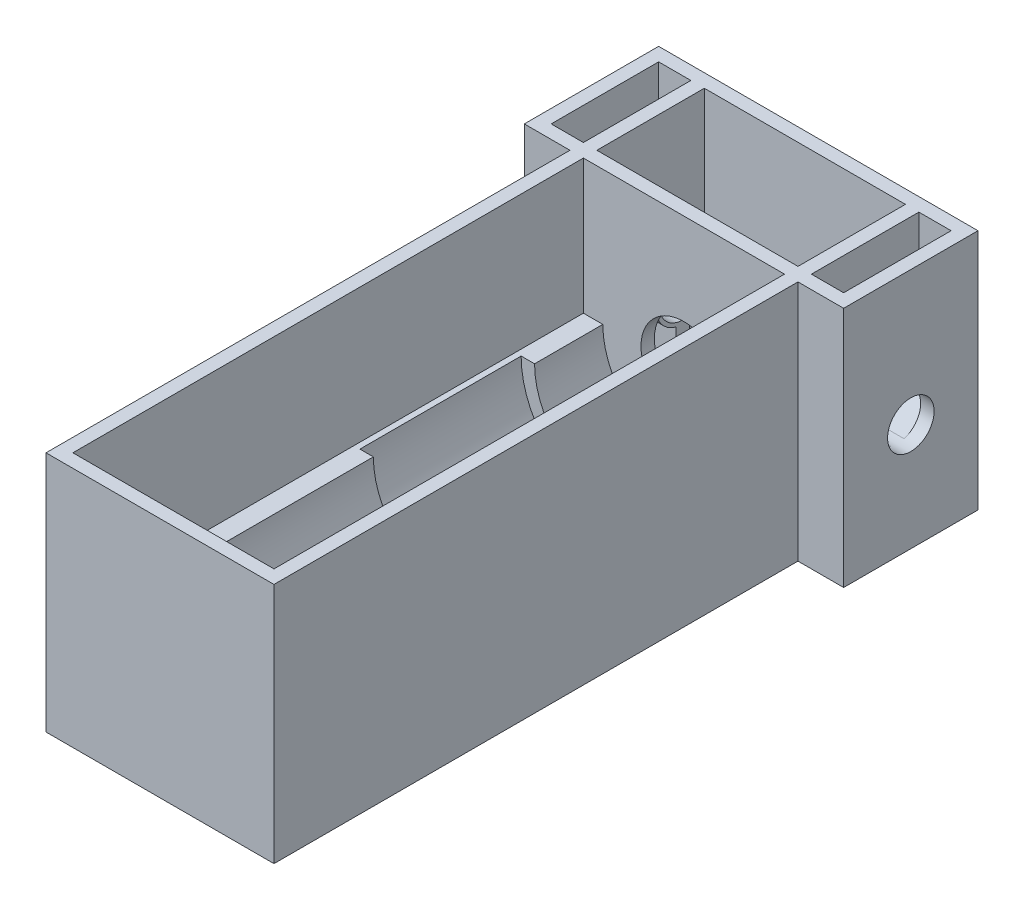
SolidWorks part; units mm, degrees
ref_plane "Front Plane" through (0, 0, 0) normal (0, 0, 1) x (1, 0, 0)
ref_plane "Top Plane" through (0, 0, 0) normal (0, 1, 0) x (1, 0, 0)
ref_plane "Right Plane" through (0, 0, 0) normal (1, 0, 0) x (0, 0, -1)
sketch "Sketch1" plane through (0, 0, 0) normal (0, 0, 1) x (1, 0, 0)
  line L1 (-26.9397, 0) -> (26.9397, 0)
  line L2 (-26.9397, 0) -> (-26.9397, 6.35)
  line L3 (-23.7647, 6.35) -> (23.7647, 6.35)
  line L4 (26.9397, 0) -> (26.9397, 6.35)
  line L6 (-26.9397, 6.35) -> (-26.9397, 57.15)
  line L7 (-26.9397, 57.15) -> (-23.7647, 57.15)
  line L8 (-23.7647, 6.35) -> (-23.7647, 57.15)
  line L10 (26.9397, 6.35) -> (26.9397, 57.15)
  line L11 (26.9397, 57.15) -> (23.7647, 57.15)
  line L12 (23.7647, 6.35) -> (23.7647, 57.15)
  dimension "D1" = 3.175
  dimension "D2" = 53.8795
  dimension "D3" = 6.35
  dimension "D4" = 50.8
extrude "Boss-Extrude1" add sketch "Sketch1" along normal mid plane 25.4
sketch "Sketch2" plane through (0, 0, -12.7) normal (0, 0, -1) x (-1, 0, 0)
  line L0 (26.9397, 0) -> (-26.9397, 0) construction
  line L1 (-26.9397, 57.15) -> (26.9397, 57.15)
  line L2 (-26.9397, 57.15) -> (-26.9397, 0)
  line L3 (-26.9397, 0) -> (26.9397, 0)
  line L4 (26.9397, 57.15) -> (26.9397, 0)
extrude "Boss-Extrude2" add sketch "Sketch2" along normal blind 3.175
sketch "Sketch6" plane through (0, 0, 0) normal (0, 0, 1) x (1, 0, 0)
  line L0 (-23.7647, 25.4) -> (-16.1447, 25.4)
  line L3 (-16.1447, 25.4) -> (-16.1447, 31.75)
  line L4 (-16.1447, 31.75) -> (-21.2247, 31.75)
  line L5 (-21.2247, 31.75) -> (-23.7647, 33.02)
  line L6 (0, 25.4) -> (0, 0) construction
  line L7 (-23.7647, 33.02) -> (-23.7647, 25.4)
  line L9 (-23.7647, 6.35) -> (-23.7647, 57.15) construction
  line L10 (23.7647, 33.02) -> (23.7647, 25.4)
  line L11 (21.2247, 31.75) -> (23.7647, 33.02)
  line L12 (16.1447, 31.75) -> (21.2247, 31.75)
  line L13 (16.1447, 25.4) -> (16.1447, 31.75)
  line L15 (23.7647, 25.4) -> (16.1447, 25.4)
  dimension "D1" = 6.35
  dimension "D2" = 5.08
  dimension "D3" = 7.62
  dimension "D4" = 7.62
  dimension "D5" = 25.4
revolve "Revolve2" add sketch "Sketch6" angle 360 about L0
sketch "Sketch3" plane through (0, 0, 0) normal (1, 0, 0) x (0, 0, -1)
  circle A0 centre (0, 25.4) radius 5.5
  circle A1 centre (0, 25.4) radius 6.35 construction
  dimension "D2" = 11
extrude "Cut-Extrude2" cut sketch "Sketch3" against normal through all both and the other way through all
sketch "Sketch5" plane through (0, 0, 0) normal (0, -1, 0) x (1, 0, 0)
  line L1 (26.9397, -15.875) -> (-26.9397, -15.875)
  line L2 (26.9397, -15.875) -> (26.9397, -41.275)
  line L3 (26.9397, -41.275) -> (-26.9397, -41.275)
  line L4 (-26.9397, -15.875) -> (-26.9397, -41.275)
  circle A0 centre (7.8897, -28.575) radius 3.4925
  circle A1 centre (-17.5103, -28.575) radius 3.4925
  point P9 (26.9397, -28.575)
  dimension "D2" = 6.985
  dimension "D1" = 25.4
  dimension "D3" = 19.05
  dimension "D4" = 2
extrude "Boss-Extrude3" add sketch "Sketch5" against normal blind 6.35
sketch "Sketch7" plane through (0, 0, 0) normal (0, 0, 1) x (1, 0, 0)
  line L0 (23.7647, 6.35) -> (-23.7647, 6.35) construction
  line L1 (-23.7647, 21.9594) -> (-16.1447, 21.9594)
  line L2 (-23.7647, 21.9594) -> (-23.7647, 6.35)
  line L3 (-23.7647, 6.35) -> (-16.1447, 6.35)
  line L4 (-16.1447, 21.9594) -> (-16.1447, 6.35)
  line L5 (-23.7647, 21.9594) -> (-16.1447, 6.35) construction
  line L6 (-23.7647, 6.35) -> (-16.1447, 21.9594) construction
  line L8 (0, 0) -> (0, 25.6446) construction
  line L9 (-26.9397, 0) -> (26.9397, 0) construction
  line L10 (23.7647, 6.35) -> (16.1447, 21.9594) construction
  line L11 (23.7647, 21.9594) -> (16.1447, 6.35) construction
  line L12 (16.1447, 21.9594) -> (16.1447, 6.35)
  line L13 (23.7647, 6.35) -> (16.1447, 6.35)
  line L14 (23.7647, 21.9594) -> (23.7647, 6.35)
  line L15 (23.7647, 21.9594) -> (16.1447, 21.9594)
  line L16 (-23.7647, 6.35) -> (-23.7647, 57.15) construction
  line L17 (-16.1447, 19.05) -> (-16.1447, 31.75) construction
  point P4 (-19.9547, 14.1547)
  point P18 (19.9547, 14.1547)
extrude "Boss-Extrude7" add sketch "Sketch7" along normal mid plane 3.175
sketch "Sketch8" plane through (0, 0, 12.7) normal (0, 0, 1) x (1, 0, 0)
  line L1 (-26.9397, 57.15) -> (26.9397, 57.15)
  line L2 (-26.9397, 57.15) -> (-26.9397, 0)
  line L3 (-26.9397, 0) -> (26.9397, 0)
  line L4 (26.9397, 57.15) -> (26.9397, 0)
  line L5 (-26.9397, 57.15) -> (26.9397, 0) construction
  line L6 (-26.9397, 0) -> (26.9397, 57.15) construction
  point P4 (0, 28.575)
extrude "Boss-Extrude8" add sketch "Sketch8" along normal blind 127
sketch "Sketch9" plane through (0, 0, 0) normal (1, 0, 0) x (0, 0, -1)
  line L0 (0, 25.4) -> (-139.7, 25.4) construction
  line L1 (-139.7, 0) -> (-139.7, 57.15) construction
  line L2 (-70.104, 47.752) -> (-70.104, 44.577)
  line L3 (-70.104, 47.752) -> (-32.004, 47.752)
  line L4 (-32.004, 47.752) -> (-32.004, 44.577)
  line L5 (-32.004, 44.577) -> (-20.1041, 44.577)
  line L6 (0, 35.56) -> (0, 25.4)
  line L7 (0, 25.4) -> (12.7, 25.4) construction
  line L8 (12.7, 6.35) -> (12.7, 57.15) construction
  line L9 (0, 25.4) -> (-70.104, 25.4)
  line L10 (-70.104, 44.577) -> (-136.525, 44.577)
  line L11 (-136.525, 44.577) -> (-136.525, 25.4)
  line L12 (-136.525, 25.4) -> (-70.104, 25.4)
  line L13 (-20.1041, 44.577) -> (-20.1041, 35.56)
  line L14 (-20.1041, 35.56) -> (0, 35.56)
  dimension "D1" = 38.1
  dimension "D2" = 10.16
  dimension "D3" = 22.352
  dimension "D4" = 3.175
  dimension "D5" = 3.175
revolve "Cut-Revolve1" cut sketch "Sketch9" angle 360 about L9
ref_axis "Axis2" through (0, 25.4, 70.104) along (0, 0, -1)
ref_axis "Axis3" through (-26.9397, 25.4, 0) along (1, 0, 0)
ref_plane "Plane2" through (0, 25.4, 0) normal (0, -1, 0) x (-1, 0, 0)
sketch "Sketch13" plane through (0, 0, 0) normal (0, -1, 0) x (-1, 0, 0)
  line L0 (26.9397, -139.7) -> (26.9397, 41.275) construction
  line L1 (26.9397, -15.4709) -> (26.9421, -15.4709)
  line L2 (26.9397, -15.4709) -> (26.9397, -139.7)
  line L3 (26.9397, -139.7) -> (26.9421, -139.7)
  line L4 (26.9421, -15.4709) -> (26.9421, -139.7)
  line L5 (26.9397, -15.4709) -> (26.9421, -139.7) construction
  line L6 (26.9397, -139.7) -> (26.9421, -15.4709) construction
  line L7 (26.9397, -139.7) -> (-26.9397, -139.7) construction
  line L9 (-26.9397, -139.7) -> (-26.9374, -139.7)
  line L10 (-26.9397, -139.7) -> (-26.9397, -15.4709)
  line L11 (-26.9397, -15.4709) -> (-26.9374, -15.4709)
  line L12 (-26.9374, -139.7) -> (-26.9374, -15.4709)
  line L13 (-26.9397, -139.7) -> (-26.9374, -15.4709) construction
  line L14 (-26.9397, -15.4709) -> (-26.9374, -139.7) construction
  point P4 (26.9409, -77.5855)
  point P13 (-26.9386, -77.5855)
extrude "Cut-Extrude7" cut sketch "Sketch13" against normal through all both and the other way through all
sketch "Sketch14" plane through (0, 57.15, 0) normal (0, 1, 0) x (1, 0, 0)
  line L1 (23.7624, -136.525) -> (-23.7647, -136.525)
  line L2 (23.7624, -136.525) -> (23.7624, -15.875)
  line L3 (23.7624, -15.875) -> (-23.7647, -15.875)
  line L4 (-23.7647, -136.525) -> (-23.7647, -15.875)
  line L5 (23.7624, -136.525) -> (-23.7647, -15.875) construction
  line L6 (23.7624, -15.875) -> (-23.7647, -136.525) construction
  line L7 (26.9374, -139.7) -> (-26.9397, -139.7) construction
  line L8 (26.9374, -139.7) -> (26.9374, -15.4709) construction
  line L10 (23.7647, -12.7) -> (-23.7647, -12.7) construction
  line L11 (-26.9397, -139.7) -> (-26.9397, 15.875) construction
  point P4 (-0.0012, -76.2)
  dimension "D1" = 3.175
  dimension "D2" = 3.175
  dimension "D3" = 3.175
  dimension "D4" = 3.175
extrude "Cut-Extrude8" cut sketch "Sketch14" against normal up to surface (31.75 mm away) up to plane "Plane2"
sketch "Sketch15" plane through (0, 0, 20.1041) normal (0, 0, 1) x (1, 0, 0)
  line L2 (-10.16, 25.4) -> (-19.177, 25.4)
  line L3 (19.177, 25.4) -> (10.16, 25.4)
  line L4 (-10.16, 25.4) -> (-19.177, 25.4)
  line L5 (19.177, 25.4) -> (10.16, 25.4)
  arc A2 (-19.177, 25.4) -> (19.177, 25.4) centre (0, 25.4) ccw
  arc A3 (-10.16, 25.4) -> (10.16, 25.4) centre (0, 25.4) ccw
  arc A4 (-19.177, 25.4) -> (19.177, 25.4) centre (0, 25.4) ccw
  arc A5 (-10.16, 25.4) -> (10.16, 25.4) centre (0, 25.4) ccw
  dimension "D1" = 0
extrude "Cut-Extrude9" cut sketch "Sketch15" against normal up to surface (4.2291 mm away) up to face at (-0.0008, 37.6767, 15.875)
sketch "Sketch16" plane through (0, 6.35, 0) normal (0, 1, 0) x (1, 0, 0)
  line L1 (26.9397, 41.275) -> (-26.9397, 41.275)
  line L2 (26.9397, 41.275) -> (26.9397, 15.875)
  line L3 (26.9397, 15.875) -> (-26.9397, 15.875)
  line L4 (-26.9397, 41.275) -> (-26.9397, 15.875)
  line L5 (26.9397, 41.275) -> (-26.9397, 15.875) construction
  line L6 (26.9397, 15.875) -> (-26.9397, 41.275) construction
  point P4 (0, 28.575)
extrude "Cut-Extrude10" cut sketch "Sketch16" against normal through all
sketch "Sketch18" plane through (0, 0, 0) normal (0, 1, 0) x (1, 0, 0)
  line L0 (-26.9397, 15.875) -> (26.9397, 15.875) construction
  line L1 (-23.7647, 15.875) -> (-37.7347, 15.875)
  line L2 (-23.7647, 15.875) -> (-23.7647, -15.875)
  line L3 (-23.7647, -15.875) -> (-37.7347, -15.875)
  line L4 (-37.7347, 15.875) -> (-37.7347, -15.875)
  line L5 (-23.7647, 15.875) -> (-37.7347, -15.875) construction
  line L6 (-23.7647, -15.875) -> (-37.7347, 15.875) construction
  line L7 (-23.7647, -12.7) -> (-23.7647, 12.7) construction
  line L8 (-19.177, -15.875) -> (-23.7647, -15.875) construction
  line L9 (-26.9397, -139.7) -> (-26.9397, 15.875) construction
  line L10 (-34.5597, 12.7) -> (-26.9397, 12.7)
  line L11 (-34.5597, 12.7) -> (-34.5597, -12.7)
  line L12 (-34.5597, -12.7) -> (-26.9397, -12.7)
  line L13 (-26.9397, 12.7) -> (-26.9397, -12.7)
  line L14 (-34.5597, 12.7) -> (-26.9397, -12.7) construction
  line L15 (-34.5597, -12.7) -> (-26.9397, 12.7) construction
  point P4 (-30.7497, 0)
  point P15 (-30.7497, 0)
  dimension "D1" = 7.62
  dimension "D2" = 3.175
  dimension "D3" = 3.175
extrude "Boss-Extrude10" add sketch "Sketch18" along normal up to surface (57.15 mm away) up to face at (-0.0012, 57.15, 76.2)
sketch "Sketch19" plane through (0, 0, 0) normal (1, 0, 0) x (0, 0, -1)
  line L0 (1.5875, 20.1341) -> (12.7, 23.4841)
  line L1 (12.7, 6.35) -> (12.7, 57.15) construction
  line L2 (-1.5875, 20.1341) -> (-12.7, 23.4841)
  line L3 (-12.7, 15.24) -> (-12.7, 35.56) construction
  line L4 (-12.7, 23.4841) -> (-12.7, 0)
  line L5 (-12.7, 0) -> (12.7, 0)
  line L6 (12.7, 0) -> (12.7, 23.4841)
  arc A0 (-1.5875, 20.1341) -> (1.5875, 20.1341) centre (0, 25.4) ccw
  circle A1 centre (0, 25.4) radius 5.5 construction
  dimension "D1" = 3.175
extrude "Boss-Extrude11" add sketch "Sketch19" against normal up to next from surface starting at face at (-26.9397, 28.575, 0)
mirror "Mirror4" about plane through (0, 0, 0) normal (1, 0, 0) of "Boss-Extrude10"
extrude "Boss-Extrude12" add sketch "Sketch19<2>" along normal up to next from surface starting at face at (26.9397, 28.575, 0)
sketch "Sketch19<2>" plane through (0, 0, 0) normal (1, 0, 0) x (0, 0, -1) same geometry as "Sketch19"
sketch "Sketch20" plane through (-23.7647, 0, 0) normal (1, 0, 0) x (0, 0, -1)
  circle A0 centre (0, 25.4) radius 5.5 construction
  circle A1 centre (0, 25.4) radius 5.5
extrude "Cut-Extrude11" cut sketch "Sketch20" against normal through all both and the other way through all
ref_axis "Axis4" through (0, 25.4, 15.875) along (0, 0, -1)
